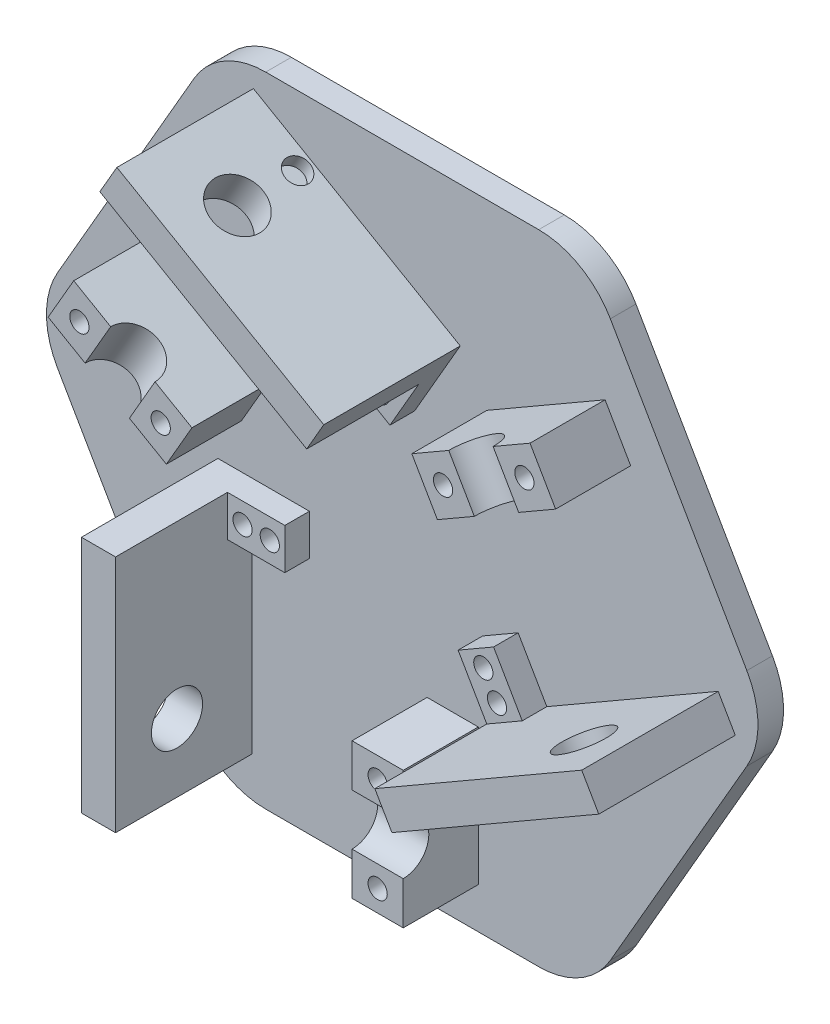
SolidWorks part; units mm, degrees
ref_plane "Front Plane" through (0, 0, 0) normal (0, 0, 1) x (1, 0, 0)
ref_plane "Top Plane" through (0, 0, 0) normal (0, 1, 0) x (1, 0, 0)
ref_plane "Right Plane" through (0, 0, 0) normal (1, 0, 0) x (0, 0, -1)
sketch "Sketch2" plane through (0, 0, 0) normal (0, 0, 1) x (1, 0, 0)
  line L1 (64.1346, 7.6987) -> (38.7346, 51.6928)
  line L2 (25.4, 59.3916) -> (-25.4, 59.3916)
  line L3 (-38.7346, 51.6928) -> (-64.1346, 7.6987)
  line L4 (-64.1346, -7.6987) -> (-38.7346, -51.6928)
  line L5 (-25.4, -59.3916) -> (25.4, -59.3916)
  line L6 (38.7346, -51.6928) -> (64.1346, -7.6987)
  circle A0 centre (0, 0) radius 59.3916 construction
  arc A1 (38.7346, 51.6928) -> (25.4, 59.3916) centre (25.4, 43.9941) ccw
  arc A2 (64.1346, 7.6987) -> (64.1346, -7.6987) centre (50.8, 0) cw
  arc A3 (25.4, -59.3916) -> (38.7346, -51.6928) centre (25.4, -43.9941) ccw
  arc A4 (-38.7346, -51.6928) -> (-25.4, -59.3916) centre (-25.4, -43.9941) ccw
  arc A5 (-64.1346, 7.6987) -> (-64.1346, -7.6987) centre (-50.8, 0) ccw
  arc A6 (-25.4, 59.3916) -> (-38.7346, 51.6928) centre (-25.4, 43.9941) ccw
  dimension "D1" = 50.8
  dimension "D2" = 59.3916
extrude "Boss-Extrude1" add sketch "Sketch2" along normal blind 4.7625
sketch "Sketch4" plane through (0, 0, 4.7625) normal (0, 0, 1) x (1, 0, 0)
  line L0 (-25.4, -59.3916) -> (25.4, -59.3916) construction
  line L1 (-34.2896, -51.7716) -> (-27.9396, -51.7716)
  line L2 (-34.2896, -51.7716) -> (-34.2896, -7.3216)
  line L3 (-34.2896, -7.3216) -> (-27.9396, -7.3216)
  line L4 (-27.9396, -51.7716) -> (-27.9396, -7.3216)
  point P17 (0, 0)
  dimension "D1" = 6.35
  dimension "D2" = 44.45
  dimension "D3" = 7.62
  dimension "D4" = 4.445
extrude "Boss-Extrude3" add sketch "Sketch4" along normal blind 25.4
sketch "Sketch5" plane through (0, 0, 4.7625) normal (0, 0, 1) x (1, 0, 0)
  line L0 (-25.4, -59.3916) -> (25.4, -59.3916) construction
  line L1 (4.6359, -51.7716) -> (14.1609, -51.7716)
  line L2 (4.6359, -51.7716) -> (4.6359, -26.3716)
  line L3 (4.6359, -26.3716) -> (14.1609, -26.3716)
  line L4 (14.1609, -51.7716) -> (14.1609, -26.3716)
  line L5 (-27.9396, -51.7716) -> (-27.9396, -7.3216) construction
  point P19 (0, 0)
  dimension "D1" = 9.525
  dimension "D2" = 25.4
  dimension "D3" = 7.62
  dimension "D4" = 32.5755
extrude "Boss-Extrude4" add sketch "Sketch5" along normal blind 13.97
sketch "Sketch6" plane through (0, 0, 4.7625) normal (0, 0, 1) x (1, 0, 0)
  line L1 (-27.9396, -7.3216) -> (-17.2716, -7.3216)
  line L2 (-27.9396, -7.3216) -> (-27.9396, -14.9416)
  line L3 (-27.9396, -14.9416) -> (-17.2716, -14.9416)
  line L4 (-17.2716, -7.3216) -> (-17.2716, -14.9416)
  line L12 (-34.2896, -7.3216) -> (-34.2896, -51.7716) construction
  point P16 (0, 0)
  dimension "D1" = 7.62
  dimension "D2" = 17.018
extrude "Boss-Extrude5" add sketch "Sketch6" along normal blind 4.572
sketch "Sketch7" plane through (0, 0, 9.3345) normal (0, 0, 1) x (1, 0, 0)
  line L0 (-27.9396, -14.9416) -> (-17.2716, -14.9416) construction
  line L1 (-17.2716, -14.9416) -> (-17.2716, -7.3216) construction
  circle A0 centre (-25.1456, -11.1316) radius 1.7907
  circle A1 centre (-20.0656, -11.1316) radius 1.7907
  dimension "D1" = 3.5814
  dimension "D2" = 3.81
  dimension "D3" = 5.08
  dimension "D4" = 2.794
sketch "Sketch8" plane through (0, 0, 18.7325) normal (0, 0, 1) x (1, 0, 0)
  line L0 (14.1609, -51.7716) -> (14.1609, -26.3716) construction
  line L1 (14.1609, -26.3716) -> (4.6359, -26.3716) construction
  circle A0 centre (9.3984, -30.334) radius 1.7907
  circle A1 centre (9.3984, -47.8092) radius 1.7907
  dimension "D1" = 3.5814
  dimension "D2" = 4.7625
  dimension "D3" = 17.4752
  dimension "D4" = 3.9624
extrude "Cut-Extrude1" cut sketch "Sketch7" against normal blind 6.731
extrude "Cut-Extrude2" cut sketch "Sketch8" against normal blind 6.731
sketch "Sketch9" plane through (-34.2896, 0, 0) normal (-1, 0, 0) x (0, 0, 1)
  line L0 (4.7625, -7.3216) -> (4.7625, -51.7716) construction
  line L1 (30.1625, -51.7716) -> (4.7625, -51.7716) construction
  circle A0 centre (7.5311, -39.0716) radius 2.286
  dimension "D1" = 4.572
  dimension "D2" = 2.7686
  dimension "D3" = 12.7
sketch "Sketch10" plane through (-34.2896, 0, 0) normal (-1, 0, 0) x (0, 0, 1)
  line L0 (30.1625, -51.7716) -> (4.7625, -51.7716) construction
  circle A0 centre (18.7325, -39.0716) radius 4.7625
  dimension "D1" = 9.525
  dimension "D2" = 11.2014
  dimension "D3" = 12.7
extrude "Cut-Extrude3" cut sketch "Sketch9" against normal blind 2.54
extrude "Cut-Extrude4" cut sketch "Sketch10" against normal up to surface (6.35 mm away) up to face at (-27.9396, -24.6782, 14.7532)
sketch "Sketch11" plane through (4.6359, 0, 0) normal (-1, 0, 0) x (0, 0, 1)
  line L0 (18.7325, -26.3716) -> (18.7325, -51.7716) construction
  circle A0 centre (18.7325, -39.0716) radius 4.7625
  dimension "D1" = 9.525
extrude "Cut-Extrude5" cut sketch "Sketch11" against normal up to surface (9.525 mm away) up to face at (14.1609, -39.0716, 11.7475)
sketch3d "3DSketch1"
  line L0 (0, 0, 0) -> (0, 0, 50000) construction
pattern_circular "CirPattern1" count 3 over 360 about axis through (0, 0, 0) along (0, 0, 1) of "Boss-Extrude3", "Boss-Extrude4", "Boss-Extrude5", "Cut-Extrude1", "Cut-Extrude2", "Cut-Extrude3", "Cut-Extrude4", "Cut-Extrude5"
